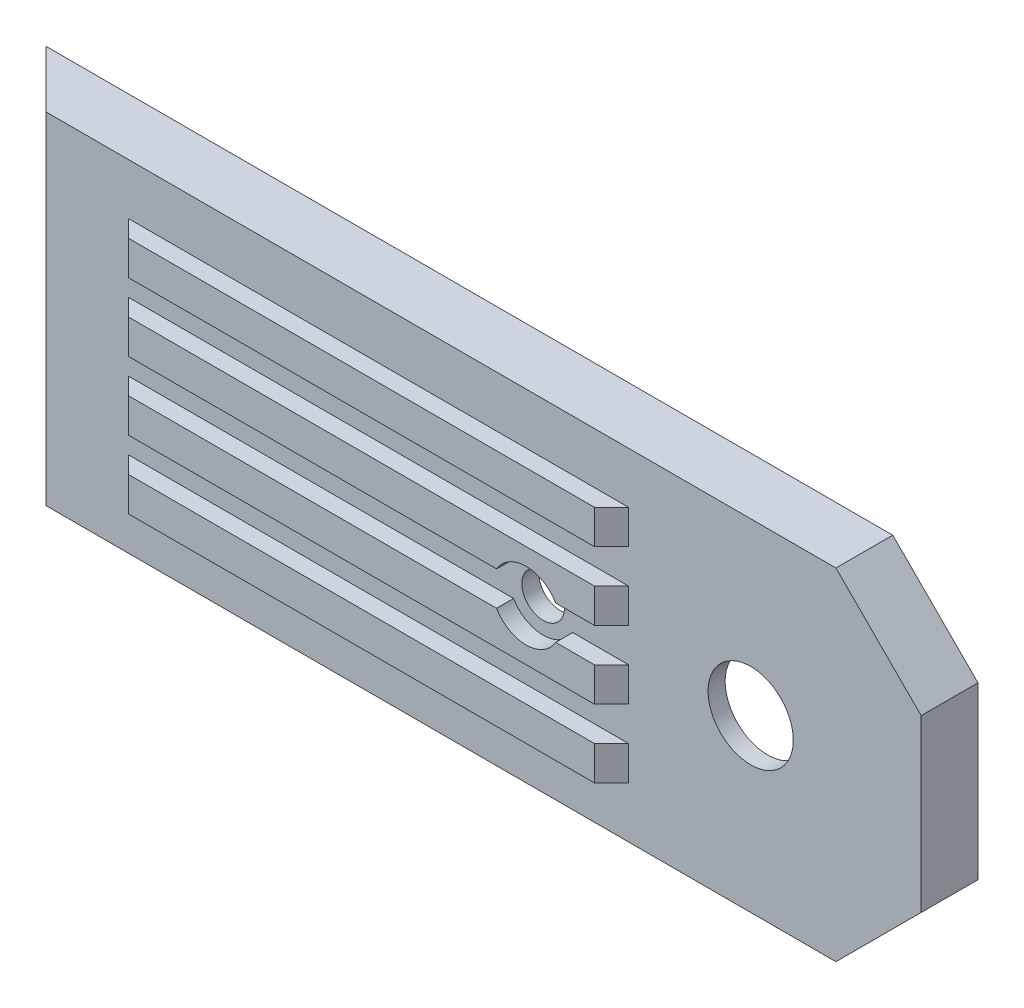
SolidWorks part; units mm, degrees
material "PLA"
ref_plane "Front Plane" through (0, 0, 0) normal (0, 0, 1) x (1, 0, 0)
ref_plane "Top Plane" through (0, 0, 0) normal (0, 1, 0) x (1, 0, 0)
ref_plane "Right Plane" through (0, 0, 0) normal (1, 0, 0) x (0, 0, -1)
sketch "Sketch1" plane through (0, 0, 0) normal (0, 0, 1) x (1, 0, 0)
  line L0 (37.25, 15) -> (44.75, 7.5)
  line L1 (-37.25, -15) -> (37.25, -15)
  line L2 (-37.25, -15) -> (-37.25, 15)
  line L3 (-37.25, 15) -> (37.25, 15)
  line L4 (44.75, -7.5) -> (44.75, 7.5)
  line L6 (44.75, -4.309) -> (47.6608, -4.5892) construction
  line L7 (37.25, -15) -> (44.75, -7.5)
  point P0 (0, 0)
  point P10 (-37.25, 0)
  point P12 (0, 15)
  dimension "D1" = 15
  dimension "D2" = 30
  dimension "D3" = 45
  dimension "D4" = 45
  dimension "D5" = 82
extrude "Boss-Extrude1" add sketch "Sketch1" along normal blind 5
chamfer "Chamfer1" distance 5 angle 45 1 edges at (-37.25, 0, 5)
sketch "Sketch2" plane through (0, 0, 0) normal (0, 0, -1) x (-1, 0, 0)
  line L0 (-29.75, -11) -> (6.75, -11)
  line L1 (-44.75, -7.5) -> (-44.75, 7.5) construction
  line L2 (-29.75, 11) -> (6.75, 11)
  arc A0 (-29.75, 11) -> (-29.75, -11) centre (-29.75, 0) ccw
  arc A1 (6.75, -11) -> (6.75, 11) centre (6.75, 0) ccw
  dimension "D1" = 22
  dimension "D2" = 15
  dimension "D4" = 36.5
extrude "Cut-Extrude1" cut sketch "Sketch2" against normal blind 3.5
sketch "Sketch3" plane through (0, 0, 3.5) normal (0, 0, -1) x (-1, 0, 0)
  line L0 (-44.75, -7.5) -> (-44.75, 7.5) construction
  circle A0 centre (6.5, 0) radius 5
  dimension "D1" = 10
  dimension "D2" = 51.25
extrude "Cut-Extrude2" cut sketch "Sketch3" against normal blind 0.75
chamfer "Chamfer2" distance 0.75 angle 45 1 edges at (-11.5, 0, 3.5)
sketch "Sketch4" plane through (0, 0, 3.5) normal (0, 0, -1) x (-1, 0, 0)
  circle A0 centre (-11.49, 0) radius 1.875
  circle A2 centre (-29.75, 0) radius 3.75
  dimension "D1" = 18.26
  dimension "D2" = 3.75
  dimension "D3" = 7.5
extrude "Cut-Extrude3" cut sketch "Sketch4" against normal through all
sketch "Sketch5" plane through (0, 0, 5) normal (0, 0, 1) x (1, 0, 0)
  line L0 (29.75, 0) -> (14.49, 0) construction
  line L1 (-32.25, 15) -> (-32.25, -15) construction
  line L2 (-25, 10.5) -> (19, 10.5)
  line L3 (-25, 4.5) -> (19, 4.5)
  line L4 (-25, 4.5) -> (-25, 1.5)
  line L5 (-25, 1.5) -> (8.8919, 1.5)
  line L6 (19, 4.5) -> (19, 1.5)
  line L7 (-25, 10.5) -> (-25, 7.5)
  line L8 (-25, 7.5) -> (19, 7.5)
  line L9 (19, 10.5) -> (19, 7.5)
  line L10 (-25, -10.5) -> (-25, -7.5)
  line L11 (-25, -7.5) -> (19, -7.5)
  line L12 (19, -10.5) -> (19, -7.5)
  line L13 (-25, -10.5) -> (19, -10.5)
  line L14 (-25, -1.5) -> (8.8919, -1.5)
  line L15 (19, -4.5) -> (19, -1.5)
  line L16 (-25, -4.5) -> (19, -4.5)
  line L17 (-25, -4.5) -> (-25, -1.5)
  line L18 (14.0881, 1.5) -> (19, 1.5)
  line L19 (8.49, 0) -> (-32.25, 0) construction
  line L20 (14.0881, -1.5) -> (19, -1.5)
  arc A0 (8.8919, -1.5) -> (14.0881, -1.5) centre (11.49, 0) ccw
  arc A1 (14.0881, 1.5) -> (8.8919, 1.5) centre (11.49, 0) ccw
  dimension "D7" = 6
  dimension "D1" = 3
  dimension "D2" = 44
  dimension "D3" = 10.75
  dimension "D4" = 1.5
  dimension "D5" = 3
  dimension "D6" = 3
extrude "Boss-Extrude2" add sketch "Sketch5" along normal blind 1.5
chamfer "Chamfer3" distance 1.5 angle 45 8 edges at (-25, 9, 6.5) (-25, 3, 6.5) (-25, -3, 6.5) (-25, -9, 6.5) (19, -9, 6.5) (19, -3, 6.5) (19, 3, 6.5) (19, 9, 6.5)
